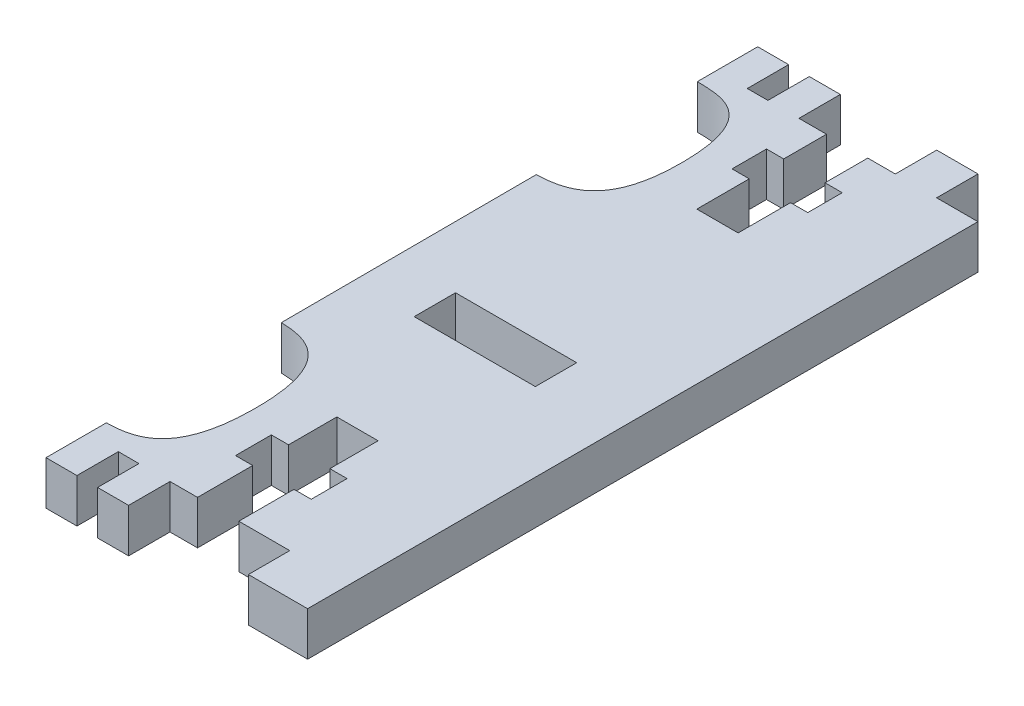
SolidWorks part; units mm, degrees
material "Acrylic (Medium-high impact)"
ref_plane "Front Plane" through (0, 0, 0) normal (0, 0, 1) x (1, 0, 0)
ref_plane "Top Plane" through (0, 0, 0) normal (0, 1, 0) x (1, 0, 0)
ref_plane "Right Plane" through (0, 0, 0) normal (1, 0, 0) x (0, 0, -1)
sketch "Sketch1" plane through (0, 0, 0) normal (0, 1, 0) x (1, 0, 0)
  line L0 (-9.4831, -21.4709) -> (-9.4831, -25.851)
  line L1 (-9.4831, 21.3709) -> (-9.4831, 25.751)
  line L2 (-9.4831, 25.751) -> (-7.2402, 25.751)
  line L3 (6.4884, 25.751) -> (6.4884, 22.7509)
  line L4 (6.4884, 22.7509) -> (9.4831, 22.7509)
  line L5 (9.4831, 22.7509) -> (9.4831, -25.851)
  line L6 (-9.4831, -25.851) -> (-7.2402, -25.851)
  line L7 (-4.9911, -0.65) -> (-4.9911, -3.6501)
  line L8 (-4.9911, -3.6501) -> (3.7933, -3.6501)
  line L9 (3.7933, -3.6501) -> (3.7933, -0.65)
  line L10 (3.7933, -0.65) -> (-4.9911, -0.65)
  line L11 (-3.4938, -25.851) -> (-3.4938, -22.8508)
  line L12 (-3.4938, -22.8508) -> (-1.4973, -22.8508)
  line L13 (-1.4973, -22.8508) -> (-1.4973, -18.8507)
  line L14 (-1.4973, -18.8507) -> (-2.745, -18.8507)
  line L15 (-2.745, -18.8507) -> (-2.745, -18.7507)
  line L16 (-2.745, -18.7507) -> (-2.745, -16.2506)
  line L17 (-2.745, -16.2506) -> (-1.4973, -16.2506)
  line L18 (-1.4973, -16.2506) -> (-1.4973, -12.7504)
  line L19 (-1.4973, -12.7504) -> (1.4972, -12.7504)
  line L20 (1.4972, -12.7504) -> (1.4972, -16.2506)
  line L21 (1.4972, -16.2506) -> (2.745, -16.2506)
  line L22 (2.745, -16.2506) -> (2.745, -18.7507)
  line L23 (2.745, -18.7507) -> (2.745, -18.8507)
  line L24 (2.745, -18.8507) -> (1.4972, -18.8507)
  line L25 (1.4972, -18.8507) -> (1.4972, -22.8508)
  line L26 (1.4972, -22.8508) -> (5.1908, -22.8508)
  line L27 (5.1908, -22.8508) -> (5.1908, -25.851)
  line L28 (3.4937, 25.751) -> (3.4937, 22.7509)
  line L29 (3.4937, 22.7509) -> (1.4972, 22.7509)
  line L30 (1.4972, 22.7509) -> (1.4972, 19.6507)
  line L31 (1.4972, 19.6507) -> (2.745, 19.6507)
  line L32 (2.745, 19.6507) -> (2.745, 17.1507)
  line L33 (2.745, 17.1507) -> (1.4972, 17.1507)
  line L34 (1.4972, 17.1507) -> (1.4972, 13.3504)
  line L35 (1.4972, 13.3504) -> (-1.4973, 13.3504)
  line L36 (-1.4973, 13.3504) -> (-1.4973, 17.1507)
  line L37 (-1.4973, 17.1507) -> (-2.745, 17.1507)
  line L38 (-2.745, 17.1507) -> (-2.745, 19.6507)
  line L39 (-2.745, 19.6507) -> (-1.4973, 19.6507)
  line L40 (-1.4973, 19.6507) -> (-1.4973, 22.7509)
  line L41 (-1.4973, 22.7509) -> (-3.4938, 22.7509)
  line L42 (-3.4938, 22.7509) -> (-3.4938, 25.751)
  line L43 (-7.2402, 25.751) -> (-7.3857, 25.8302)
  line L44 (-5.7428, 25.751) -> (-5.7428, 22.7509)
  line L45 (-5.7428, 22.7509) -> (-7.2402, 22.7509)
  line L46 (-7.2402, 22.7509) -> (-7.2402, 25.751)
  line L47 (-7.2402, -22.8508) -> (-5.7428, -22.8508)
  line L48 (-5.7428, -22.8508) -> (-5.7428, -25.851)
  line L49 (-5.7428, -25.851) -> (-3.4938, -25.851)
  line L50 (-7.2402, -25.851) -> (-7.2402, -22.8508)
  line L51 (-5.7428, 25.751) -> (-3.4938, 25.751)
  line L52 (-3.4938, 25.751) -> (-3.5802, 25.8302)
  line L53 (3.4937, 25.751) -> (6.4884, 25.751)
  line L54 (-9.4831, 9.693) -> (-9.4312, -8.8341)
  line L55 (5.1908, -25.851) -> (9.4831, -25.851)
  spline S1 degree 3 poles (-9.4312, -8.8341) (-7.1882, -8.8985) (-4.9654, -9.6433) (-4.9951, -15.2629) knots 1 1 1 1 2 2 2 2
  spline S2 degree 3 poles (-4.9951, -15.2629) (-5.0248, -20.8823) (-7.4265, -21.4438) (-9.4831, -21.4709) knots 2 2 2 2 3 3 3 3
  spline S4 degree 3 poles (-9.4831, 9.693) (-7.2402, 9.7574) (-4.8898, 10.4982) (-4.9525, 15.8863) knots 5 5 5 5 6 6 6 6
  spline S5 degree 3 poles (-4.9525, 15.8863) (-5.0152, 21.2742) (-7.4265, 21.3438) (-9.4831, 21.3709) knots 6 6 6 6 7 7 7 7
extrude "Boss-Extrude1" add sketch "Sketch1" along normal blind 3.175 contours S5 S4 L54 S1 S2 L0 L6 L50 L47 L48 L49 L11 L12 L13 L14 L15 L16 L17 L18 L19 L20 L21 L22 L23 L24 L25 L26 L27 L55 L5 L4 L3 L53 L28 L29 L30 L31 L32 L33 L34 L35 L36 L37 L38 L39 L40 L41 L42 L51 L44 L45 region at (0.9417, 0, 0.0405)
